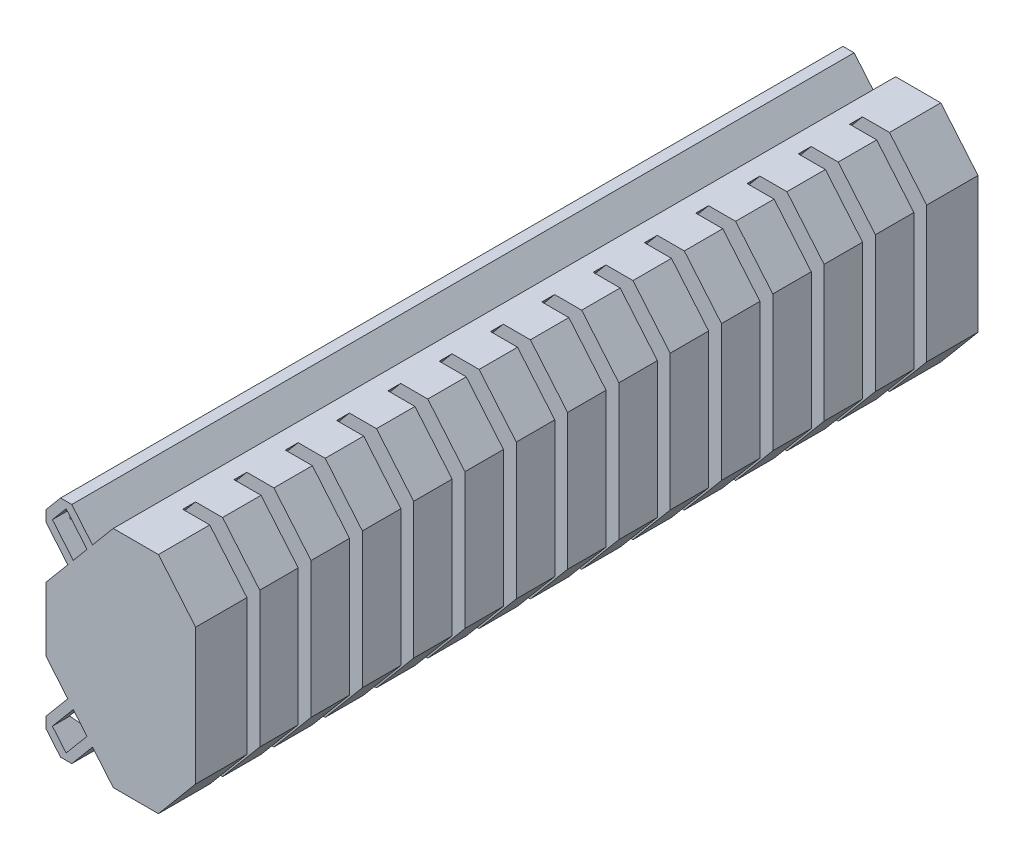
SolidWorks part; units mm, degrees
ref_plane "Ebene vorne" through (0, 0, 0) normal (0, 0, 1) x (1, 0, 0)
ref_plane "Ebene oben" through (0, 0, 0) normal (0, 1, 0) x (1, 0, 0)
ref_plane "Ebene rechts" through (0, 0, 0) normal (1, 0, 0) x (0, 0, -1)
sketch "Skizze3" plane through (0, 0, 0) normal (0, 0, 1) x (1, 0, 0)
  line L0 (-7.7197, 0) -> (0, 9.2) construction
  line L1 (0, 9.2) -> (0, -9.2) construction
  line L2 (0, -9.2) -> (-7.7197, 0) construction
  line L3 (-7.5, 0) -> (49992.5, 0) construction
  line L4 (-9, -3) -> (-9, 3)
  line L5 (-9, 3) -> (-2.7068, 10.5)
  line L6 (-2.7068, 10.5) -> (1.52, 10.5)
  line L7 (1.52, 10.5) -> (5, 6.3527)
  line L13 (0, 9.2) -> (3, 5.6247) construction
  line L14 (3, 5.6247) -> (3, -5.6247) construction
  line L15 (3, -5.6247) -> (0, -9.2) construction
  line L16 (5, 6.3527) -> (5, -6.3527)
  line L17 (-9, -3) -> (-2.7068, -10.5)
  line L18 (-2.7068, -10.5) -> (1.52, -10.5)
  line L19 (1.52, -10.5) -> (5, -6.3527)
  point P20 (-9, 0)
  point P23 (5, 0)
  dimension "D2" = 50
  dimension "D3" = 2
  dimension "D4" = 3
  dimension "D5" = 21
  dimension "D1" = 14
  dimension "D6" = 2
  dimension "D7" = 1.3
  dimension "D8" = 6
  dimension "D9" = 50
extrude "Aufsatz-Linear austragen2" add sketch "Skizze3" along normal mid plane 3.6
sketch "Skizze2" plane through (0, 0, 0) normal (0, 0, 1) x (1, 0, 0)
  line L0 (-7.5519, 0) -> (0, 9)
  line L1 (0, 9) -> (0, -9) construction
  line L2 (0, -9) -> (-7.5519, 0)
  line L3 (-7.5, 0) -> (49992.5, 0) construction
  line L13 (0, 9) -> (3, 5.4247)
  line L14 (3, 5.4247) -> (3, -5.4247)
  line L15 (3, -5.4247) -> (0, -9)
  dimension "D2" = 50
  dimension "D4" = 3
  dimension "D5" = 18
  dimension "D1" = 50
extrude "Schnitt-Linear austragen1" cut sketch "Skizze2" against normal mid plane 1
sketch "Skizze5" plane through (0, 0, 0) normal (0, 0, 1) x (1, 0, 0)
  line L0 (-7.5519, 0) -> (-6.7163, 0.9959)
  line L1 (-6.7163, 0.9959) -> (-5.8806, 0)
  line L2 (-5.8806, 0) -> (-6.7163, -0.9959)
  line L3 (-6.7163, -0.9959) -> (-7.5519, 0)
  line L4 (-7.5519, 0) -> (-50007.5519, 0) construction
  line L5 (-7.5519, 0) -> (0, -9)
  line L6 (0, -9) -> (3, -5.4247)
  line L7 (3, -5.4247) -> (3, 5.4247)
  line L8 (3, 5.4247) -> (0, 9)
  line L9 (0, 9) -> (-7.5519, 0)
  line L10 (-7.5519, 0) -> (0, -9) construction
  line L11 (0, -9) -> (3, -5.4247) construction
  line L12 (3, -5.4247) -> (3, 5.4247) construction
  line L13 (3, 5.4247) -> (0, 9) construction
  line L14 (0, 9) -> (-7.5519, 0) construction
  point P2 (0, 0)
  dimension "D2" = 1.3
  dimension "D1" = 0
extrude "Schnitt-Linear austragen2" cut sketch "Skizze5" against normal through all both and the other way through all
sketch "Skizze6" plane through (0, 0, 1.8) normal (0, 0, 1) x (1, 0, 0)
  line L0 (0, 0) -> (50000, 0) construction
  line L1 (1.52, 10.5) -> (-2.7068, 10.5) construction
  line L3 (-2.7068, 10.5) -> (-9, 3) construction
  line L4 (-1.0097, 10.5) -> (-2.7068, 10.5)
  line L5 (-9, 3) -> (-9, -3)
  line L6 (-2.7068, 10.5) -> (-9, 3)
  line L7 (-4.5806, -6.2443) -> (-4.5806, 6.2443)
  line L8 (-4.5806, 6.2443) -> (-1.0097, 10.5)
  line L9 (-9, 3) -> (-9, -3) construction
  line L10 (-4.5806, -6.2443) -> (-1.0097, -10.5)
  line L11 (-2.7068, -10.5) -> (-9, -3)
  line L12 (-1.0097, -10.5) -> (-2.7068, -10.5)
  point P11 (-4.5806, 0)
  point P14 (-9, 0)
  dimension "D1" = 1.3
  dimension "D2" = 1.3
extrude "Aufsatz-Linear austragen3" add sketch "Skizze6" along normal blind 1.2
sketch "Skizze7" plane through (0, 0, -1.8) normal (0, 0, -1) x (-1, 0, 0)
  line L4 (6.7163, -0.9959) -> (7.5519, 0)
  line L5 (7.5519, 0) -> (6.7163, 0.9959)
  line L6 (6.7163, 0.9959) -> (5.8806, 0)
  line L7 (5.8806, 0) -> (6.7163, -0.9959)
  line L8 (6.7163, -0.9959) -> (7.5519, 0)
  line L9 (7.5519, 0) -> (6.7163, 0.9959)
  line L10 (6.7163, 0.9959) -> (5.8806, 0)
  line L11 (5.8806, 0) -> (6.7163, -0.9959)
  dimension "D1" = 0
extrude "Schnitt-Linear austragen3" cut sketch "Skizze7" against normal through all
pattern_linear "Lineares Muster1" count 15 spacing 4.8 along (0, 0, 1) of "Aufsatz-Linear austragen2", "Schnitt-Linear austragen1", "Schnitt-Linear austragen2", "Aufsatz-Linear austragen3", "Schnitt-Linear austragen3"
sketch "Skizze8" plane through (0, 0, -1.8) normal (0, 0, -1) x (-1, 0, 0)
  line L8 (2.7068, -10.5) -> (9, -3)
  line L9 (9, -3) -> (9, 3)
  line L10 (9, 3) -> (2.7068, 10.5)
  line L11 (2.7068, 10.5) -> (-1.52, 10.5)
  line L12 (-1.52, 10.5) -> (-5, 6.3527)
  line L13 (-5, 6.3527) -> (-5, -6.3527)
  line L14 (-5, -6.3527) -> (-1.52, -10.5)
  line L15 (-1.52, -10.5) -> (2.7068, -10.5)
  line L16 (2.7068, -10.5) -> (9, -3)
  line L17 (9, -3) -> (9, 3)
  line L18 (9, 3) -> (2.7068, 10.5)
  line L19 (2.7068, 10.5) -> (-1.52, 10.5)
  line L20 (-1.52, 10.5) -> (-5, 6.3527)
  line L21 (-5, 6.3527) -> (-5, -6.3527)
  line L22 (-5, -6.3527) -> (-1.52, -10.5)
  line L23 (-1.52, -10.5) -> (2.7068, -10.5)
  dimension "D1" = 0
extrude "Aufsatz-Linear austragen4" add sketch "Skizze8" along normal blind 1.2 and the other way blind 0.8
sketch "Skizze9" plane through (0, 0, 69) normal (0, 0, 1) x (1, 0, 0)
  line L0 (-1.0097, 10.5) -> (-2.7068, 10.5) construction
  line L1 (-2.7068, 10.5) -> (-9, 3) construction
  line L2 (-9, 3) -> (-9, -3) construction
  line L3 (-9, -3) -> (-2.7068, -10.5) construction
  line L4 (-2.7068, -10.5) -> (-1.0097, -10.5) construction
  line L5 (-1.0097, 10.5) -> (-2.7068, 10.5)
  line L6 (-2.7068, 10.5) -> (-9, 3)
  line L7 (-9, 3) -> (-9, -3)
  line L8 (-1.0097, 10.5) -> (-4.5806, 6.2443)
  line L9 (-4.5806, 6.2443) -> (-4.5806, -6.2443)
  line L10 (-4.5806, -6.2443) -> (-1.0097, -10.5)
  line L11 (-1.0097, -10.5) -> (1.52, -10.5)
  line L12 (1.52, -10.5) -> (5, -6.3527)
  line L13 (5, -6.3527) -> (5, 6.3527)
  line L14 (5, 6.3527) -> (1.52, 10.5)
  line L15 (1.52, 10.5) -> (-1.0097, 10.5)
  line L19 (-1.0097, -10.5) -> (1.52, -10.5)
  line L20 (1.52, -10.5) -> (5, -6.3527)
  line L21 (5, -6.3527) -> (5, 6.3527)
  line L22 (5, 6.3527) -> (1.52, 10.5)
  line L23 (1.52, 10.5) -> (-1.0097, 10.5)
  line L24 (-9, -3) -> (-2.7068, -10.5)
  line L25 (-2.7068, -10.5) -> (-1.0097, -10.5)
  dimension "D1" = 0
extrude "Aufsatz-Linear austragen5" add sketch "Skizze9" along normal blind 1.2 and the other way blind 0.8
sketch "Skizze10" plane through (0, 0, -3) normal (0, 0, -1) x (-1, 0, 0)
  line L0 (2.1631, -10.5) -> (50002.1631, -10.5) construction
  line L1 (9, -2.1493) -> (9, -50002.1493) construction
  line L2 (7.1144, -9.9) -> (8.4, -8.3679)
  line L3 (8.4, -8.3679) -> (6.4479, -6.0415)
  line L6 (4.6481, -8.1864) -> (6.5894, -10.5)
  line L7 (2.7068, -10.5) -> (9, -3) construction
  line L8 (6.5894, -10.5) -> (7.6394, -10.5)
  line L9 (7.6394, -10.5) -> (9, -8.8785)
  line L10 (9, -8.8785) -> (9, -7.8573)
  line L11 (9, -7.8573) -> (6.9621, -5.4286)
  line L12 (4.6481, -8.1864) -> (5.1623, -7.5736)
  line L13 (5.8288, -8.3679) -> (5.3146, -8.9807) construction
  line L14 (6.312, -7.4116) -> (32145.6924, -38309.6337) construction
  line L15 (7.1144, -6.8358) -> (7.6287, -6.223) construction
  line L16 (6.9621, -5.4286) -> (6.4479, -6.0415)
  line L17 (5.1623, -7.5736) -> (5.8288, -8.3679) construction
  line L18 (5.8288, -8.3679) -> (7.1144, -6.8358) construction
  line L19 (7.1144, -6.8358) -> (6.4479, -6.0415) construction
  line L20 (7.7572, -9.134) -> (6.4716, -7.6019) construction
  line L21 (5.1623, -7.5736) -> (7.1144, -9.9)
  line L22 (8.4, -8.3679) -> (8.9142, -8.9807) construction
  point P27 (7.1144, -8.3679)
  dimension "D1" = 2
  dimension "D2" = 0.6
  dimension "D3" = 0.6
  dimension "D4" = 0.8
  dimension "D5" = 50
  dimension "D6" = 0.8
extrude "Aufsatz-Linear austragen6" add sketch "Skizze10" against normal up to surface (73.2 mm away) up to face at (-1.2967, 0, 70.2)
mirror "Spiegeln1" about plane through (0, 0, 0) normal (0, 1, 0) of "Aufsatz-Linear austragen6"
sketch "Skizze11" plane through (-9, 0, 0) normal (-1, 0, 0) x (0, 0, 1)
  line L0 (70.2, 6.0415) -> (-3, 6.0415) construction
  line L1 (70.2, 6.0415) -> (-3, 6.0415) construction
  line L2 (70.2, 7.5736) -> (-3, 7.5736) construction
  line L4 (70.2, 9.9) -> (-3, 9.9) construction
  line L6 (-1.7, 7.9707) -> (-0.0812, 9.9)
  line L7 (-0.0812, 9.9) -> (1.5377, 7.9707)
  line L8 (1.5377, 7.9707) -> (-0.0812, 6.0415)
  line L9 (-0.0812, 6.0415) -> (-1.7, 7.9707)
  line L10 (-3, 8.8785) -> (-3, 7.8573) construction
  line L11 (0, 0) -> (50000, 0) construction
  line L12 (33.6, -3.1716) -> (33.6, -50003.1716) construction
  line L13 (70.2, -3) -> (-3, -3) construction
  line L14 (-0.0812, -6.0415) -> (-1.7, -7.9707)
  line L15 (-1.7, -7.9707) -> (-0.0812, -9.9)
  line L16 (-0.0812, -9.9) -> (1.5377, -7.9707)
  line L17 (1.5377, -7.9707) -> (-0.0812, -6.0415)
  line L18 (65.6623, -7.9707) -> (67.2812, -6.0415)
  line L19 (67.2812, -9.9) -> (65.6623, -7.9707)
  line L20 (68.9, -7.9707) -> (67.2812, -9.9)
  line L21 (67.2812, -6.0415) -> (68.9, -7.9707)
  line L22 (67.2812, 6.0415) -> (68.9, 7.9707)
  line L23 (68.9, 7.9707) -> (67.2812, 9.9)
  line L24 (67.2812, 9.9) -> (65.6623, 7.9707)
  line L25 (65.6623, 7.9707) -> (67.2812, 6.0415)
  line L26 (70.2, 7.5736) -> (-3, 7.5736) construction
  line L27 (70.2, 9.9) -> (-3, 9.9) construction
  line L29 (70.2, 8.3679) -> (-3, 8.3679) construction
  line L30 (70.2, 8.3679) -> (-3, 8.3679) construction
  circle A0 centre (67.2812, 7.9707) radius 1.2401 construction
  point P4 (0.6882, 9.7)
  point P5 (7.375, 8.1679)
  point P19 (33.6, -3)
  point P38 (-1.8, 7.4736)
  point P39 (2.4509, 5.9415)
  point P40 (3.8339, 8.1679)
  point P41 (1.6607, 8.3834)
  point P42 (0, 0)
  dimension "D2" = 2.4802
  dimension "D1" = 1.3
  dimension "D3" = 50
  dimension "D4" = 50
extrude "Schnitt-Linear austragen4" cut sketch "Skizze11" against normal up to next
